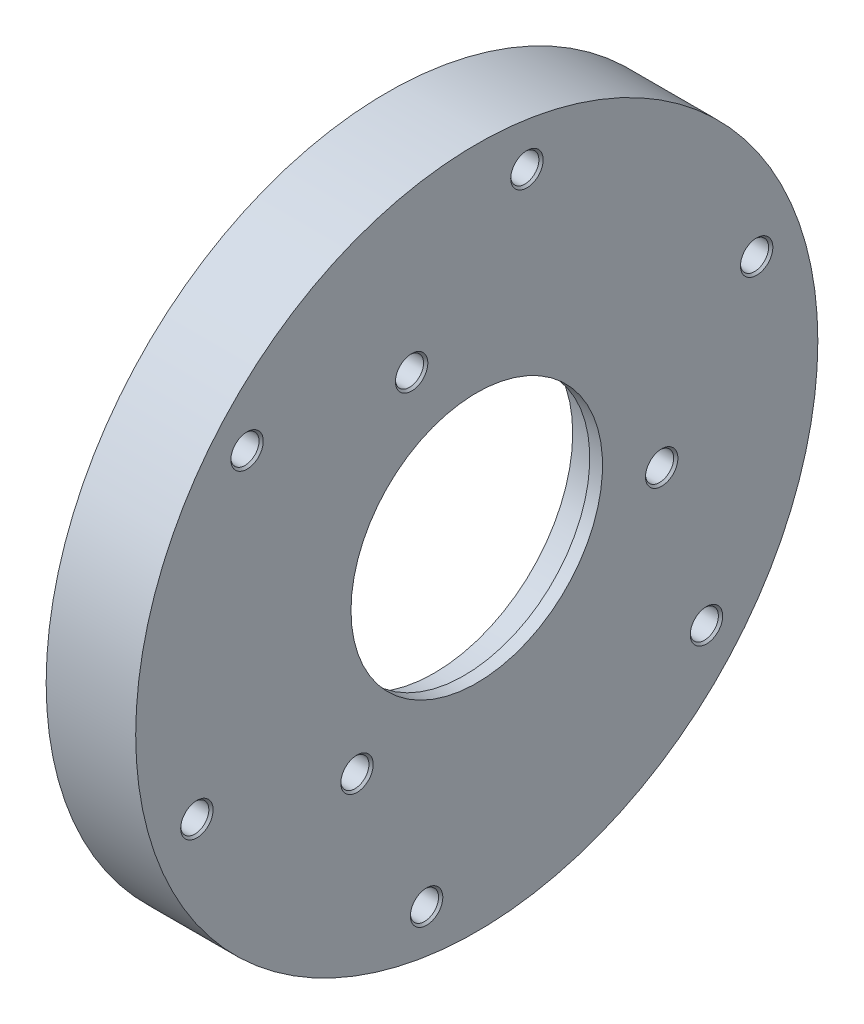
SolidWorks part; units mm, degrees
ref_plane "Front Plane" through (0, 0, 0) normal (0, 0, 1) x (1, 0, 0)
ref_plane "Top Plane" through (0, 0, 0) normal (0, 1, 0) x (1, 0, 0)
ref_plane "Right Plane" through (0, 0, 0) normal (1, 0, 0) x (0, 0, -1)
sketch "Sketch2" plane through (0, 0, 0) normal (0, 0, 1) x (1, 0, 0)
  line L0 (0, 0) -> (80.4799, 0) construction
  line L1 (0, 80) -> (0, 52.5)
  line L2 (0, 52.5) -> (11, 52.5)
  line L3 (11, 52.5) -> (11, 32.5)
  line L4 (11, 32.5) -> (18, 32.5)
  line L5 (18, 32.5) -> (18, 29.5)
  line L6 (18, 29.5) -> (21, 29.5)
  line L7 (21, 29.5) -> (21, 80)
  line L8 (21, 80) -> (0, 80)
  dimension "D1" = 80
  dimension "D2" = 32.5
  dimension "D3" = 52.5
  dimension "D4" = 18
  dimension "D5" = 3
  dimension "D6" = 7
  dimension "D7" = 3
revolve "Revolve1" add sketch "Sketch2" angle 360 about L0
sketch "Sketch3" plane through (0, 0, 0) normal (-1, 0, 0) x (0, 0, 1)
  circle A0 centre (0, 0) radius 60 construction
  circle A1 centre (0, 60) radius 2.5
  circle A2 centre (12.0779, 58.7718) radius 2.5
  circle A3 centre (23.6614, 55.1375) radius 2.5
  circle A4 centre (34.2761, 49.2458) radius 2.5
  circle A5 centre (43.4876, 41.338) radius 2.5
  circle A6 centre (50.9187, 31.7378) radius 2.5
  circle A7 centre (56.2651, 20.8383) radius 2.5
  circle A8 centre (59.3081, 9.0857) radius 2.5
  circle A9 centre (59.923, -3.039) radius 2.5
  circle A10 centre (58.0846, -15.0392) radius 2.5
  circle A11 centre (53.8683, -26.4236) radius 2.5
  circle A12 centre (47.4465, -36.7264) radius 2.5
  circle A13 centre (39.0823, -45.5255) radius 2.5
  circle A14 centre (29.1181, -52.4608) radius 2.5
  circle A15 centre (17.9618, -57.2484) radius 2.5
  circle A16 centre (6.0701, -59.6922) radius 2.5
  circle A17 centre (-6.0701, -59.6922) radius 2.5
  circle A18 centre (-17.9618, -57.2484) radius 2.5
  circle A19 centre (-29.1181, -52.4608) radius 2.5
  circle A20 centre (-39.0823, -45.5255) radius 2.5
  circle A21 centre (-47.4465, -36.7264) radius 2.5
  circle A22 centre (-53.8683, -26.4236) radius 2.5
  circle A23 centre (-58.0846, -15.0392) radius 2.5
  circle A24 centre (-59.923, -3.039) radius 2.5
  circle A25 centre (-59.3081, 9.0857) radius 2.5
  circle A26 centre (-56.2651, 20.8383) radius 2.5
  circle A27 centre (-50.9187, 31.7378) radius 2.5
  circle A28 centre (-43.4876, 41.338) radius 2.5
  circle A29 centre (-34.2761, 49.2458) radius 2.5
  circle A30 centre (-23.6614, 55.1375) radius 2.5
  circle A31 centre (-12.0779, 58.7718) radius 2.5
  point P67 (0, 0)
  dimension "D1" = 120
  dimension "D2" = 5
  dimension "D3" = 31
extrude "Cut-Extrude1" cut sketch "Sketch3" against normal blind 4
sketch "Sketch4" [suppressed] plane through (21, 0, 0) normal (1, 0, 0) x (0, 0, -1)
  circle A0 centre (-38.0255, -58.7712) radius 5.5
  circle A1 centre (-69.9102, 3.5454) radius 5.5
  circle A2 centre (-31.8846, 62.3167) radius 5.5
  circle A3 centre (38.0255, 58.7712) radius 5.5
  circle A4 centre (69.9102, -3.5454) radius 5.5
  circle A5 centre (31.8846, -62.3167) radius 5.5
  point P16 (0, 0)
  dimension "D2" = 11
  dimension "D1" = 6
extrude "Cut-Extrude2" [suppressed] cut sketch "Sketch4" against normal blind 4
sketch "Sketch5" [suppressed] plane through (21, 0, 0) normal (1, 0, 0) x (0, 0, -1)
  circle A0 centre (-38.0255, -58.7712) radius 3
  circle A1 centre (-69.9102, 3.5454) radius 3
  circle A2 centre (-31.8846, 62.3167) radius 3
  circle A3 centre (38.0255, 58.7712) radius 3
  circle A4 centre (69.9102, -3.5454) radius 3
  circle A5 centre (31.8846, -62.3167) radius 3
  point P16 (0, 0)
  dimension "D2" = 6
  dimension "D1" = 6
extrude "Cut-Extrude3" [suppressed] cut sketch "Sketch5" against normal through all
sketch "Sketch6" plane through (0, 0, 0) normal (-1, 0, 0) x (0, 0, 1)
  circle A0 centre (53.8756, 44.6925) radius 3
  circle A1 centre (65.6426, -24.3114) radius 3
  circle A2 centre (11.7671, -69.0039) radius 3
  circle A3 centre (-53.8756, -44.6925) radius 3
  circle A4 centre (-65.6426, 24.3114) radius 3
  circle A5 centre (-11.7671, 69.0039) radius 3
  point P15 (0, 0)
  dimension "D2" = 6
  dimension "D1" = 6
extrude "Cut-Extrude4" cut sketch "Sketch6" against normal blind 11
sketch "Sketch7" plane through (21, 0, 0) normal (-1, 0, 0) x (0, 0, 1)
  circle A0 centre (53.8756, 44.6925) radius 3.3
  circle A1 centre (65.6426, -24.3114) radius 3.3
  circle A2 centre (11.7671, -69.0039) radius 3.3
  circle A3 centre (-53.8756, -44.6925) radius 3.3
  circle A4 centre (-65.6426, 24.3114) radius 3.3
  circle A5 centre (-11.7671, 69.0039) radius 3.3
  point P15 (0, 0)
  dimension "D1" = 6.6
  dimension "D2" = 6
extrude "Cut-Extrude5" cut sketch "Sketch7" along normal blind 10
sketch "Sketch8" [suppressed] plane through (21, 0, 0) normal (1, 0, 0) x (0, 0, -1)
  circle A0 centre (-23.7966, 67.4351) radius 1
  dimension "D1" = 2
extrude "Cut-Extrude6" [suppressed] cut sketch "Sketch8" against normal blind 2
sketch "Sketch9" plane through (0, 0, 0) normal (-1, 0, 0) x (0, 0, 1)
  circle A0 centre (2.5177, -71.4663) radius 1
  dimension "D1" = 2
extrude "Cut-Extrude7" cut sketch "Sketch9" against normal blind 2
sketch "Sketch10" plane through (21, 0, 0) normal (1, 0, 0) x (0, 0, -1)
  line L0 (11.7671, 69.0039) -> (-11.7671, -69.0039) construction
  line L1 (-15.2814, 41.2611) -> (0, 0) construction
  circle A0 centre (0, 0) radius 44 construction
  circle A1 centre (-15.2814, 41.2611) radius 3.3
  circle A2 centre (43.3739, -7.3964) radius 3.3
  circle A3 centre (-28.0924, -33.8647) radius 3.3
  point P15 (0, 0)
  dimension "D1" = 6.6
  dimension "D2" = 88
  dimension "D3" = 30
  dimension "D4" = 3
extrude "Cut-Extrude8" cut sketch "Sketch10" against normal up to next
chamfer "Chamfer1" distance 0.5 angle 45 9 edges at (21, -69.0039, 15.0671) (21, -44.6925, -50.5756) (21, 24.3114, -62.3426) (21, 69.0039, -8.4671) (21, 44.6925, 57.1756) (21, -24.3114, 68.9426) (21, -33.8647, 24.7924) (21, -7.3964, -46.6739) (21, 41.2611, 11.9814)
equation "\"R_ROLL\"= 5mm"
equation "\"D_SUN\"= 120mm"
equation "\"NUM_ROLL\"= 31"
equation "\"RHO\"= 1mm"
equation "\"D_SHAFT\"= 28mm"
equation "\"D_OUTPUT\"= 80mm"
equation "\"NUM_OUT\"= 8"
equation "\"R_OUT_ROLL\"= 5mm"
equation "\"D1@Sketch3\"=\"D_SUN\""
